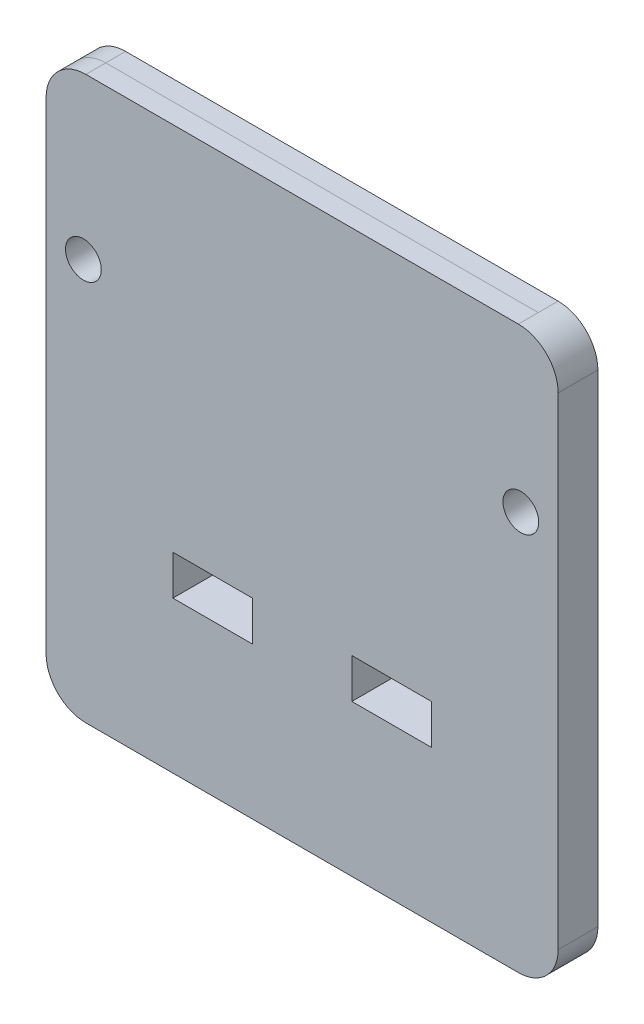
SolidWorks part; units mm, degrees
material "Pink Foam"
ref_plane "Front Plane" through (0, 0, 0) normal (0, 0, 1) x (1, 0, 0)
ref_plane "Top Plane" through (0, 0, 0) normal (0, 1, 0) x (1, 0, 0)
ref_plane "Right Plane" through (0, 0, 0) normal (1, 0, 0) x (0, 0, -1)
sketch "Sketch1" plane through (0, 0, 0) normal (0, 0, 1) x (1, 0, 0)
  line L1 (-139.7, -203.2) -> (139.7, -203.2) construction
  line L2 (-165.1, -177.8) -> (-165.1, 177.8) construction
  line L3 (-139.7, 203.2) -> (139.7, 203.2) construction
  line L4 (165.1, -177.8) -> (165.1, 177.8) construction
  line L5 (-165.1, -203.2) -> (165.1, 203.2) construction
  line L6 (-165.1, 203.2) -> (165.1, -203.2) construction
  line L7 (-138.113, -179.3553) -> (138.113, -179.3553)
  line L8 (-163.513, -153.9553) -> (-163.513, 153.9553)
  line L9 (-138.113, 179.3553) -> (138.113, 179.3553)
  line L10 (163.513, -153.9553) -> (163.513, 153.9553)
  line L11 (-163.513, -179.3553) -> (163.513, 179.3553) construction
  line L12 (-163.513, 179.3553) -> (163.513, -179.3553) construction
  arc A0 (-139.7, -203.2) -> (-165.1, -177.8) centre (-139.7, -177.8) cw construction
  arc A1 (139.7, -203.2) -> (165.1, -177.8) centre (139.7, -177.8) ccw construction
  arc A2 (139.7, 203.2) -> (165.1, 177.8) centre (139.7, 177.8) cw construction
  arc A3 (-165.1, 177.8) -> (-139.7, 203.2) centre (-139.7, 177.8) cw construction
  circle A4 centre (-139.7, 76.2) radius 11.422
  circle A5 centre (139.7, 76.2) radius 11.422
  arc A6 (-138.113, -179.3553) -> (-163.513, -153.9553) centre (-138.113, -153.9553) cw
  arc A7 (138.113, -179.3553) -> (163.513, -153.9553) centre (138.113, -153.9553) ccw
  arc A8 (138.113, 179.3553) -> (163.513, 153.9553) centre (138.113, 153.9553) cw
  arc A9 (-163.513, 153.9553) -> (-138.113, 179.3553) centre (-138.113, 153.9553) cw
  point P0 (0, 0)
  point P23 (0, 0)
  dimension "D3" = 25.4
  dimension "D7" = 22.844
  dimension "D8" = 327.026
  dimension "D10" = 25.4
  dimension "D1" = 330.2
  dimension "D2" = 406.4
  dimension "D4" = 25.4
  dimension "D5" = 127
  dimension "D6" = 25.4
  dimension "D9" = 358.7106
extrude "Boss-Extrude1" add sketch "Sketch1" along normal blind 25.4
ref_plane "Plane1" through (0, 0, 12.7) normal (0, 0, 1) x (1, 0, 0)
sketch "Sketch2" plane through (0, 0, 0) normal (0, 0, -1) x (-1, 0, 0)
  line L8 (-82.55, -82.55) -> (-31.75, -82.55)
  line L9 (-31.75, -82.55) -> (-31.75, -57.15)
  line L10 (-31.75, -57.15) -> (-82.55, -57.15)
  line L11 (-82.55, -57.15) -> (-82.55, -82.55)
  line L16 (31.75, -82.55) -> (82.55, -82.55)
  line L17 (31.75, -57.15) -> (31.75, -82.55)
  line L18 (82.55, -57.15) -> (31.75, -57.15)
  line L19 (82.55, -82.55) -> (82.55, -57.15)
  dimension "D1" = 31.75
  dimension "D2" = 82.55
  dimension "D3" = 31.75
  dimension "D4" = 57.15
  dimension "D5" = 82.55
extrude "Foam Insert Cut-Throughs" cut sketch "Sketch2" against normal blind 25.4
split line "Split Line2"
